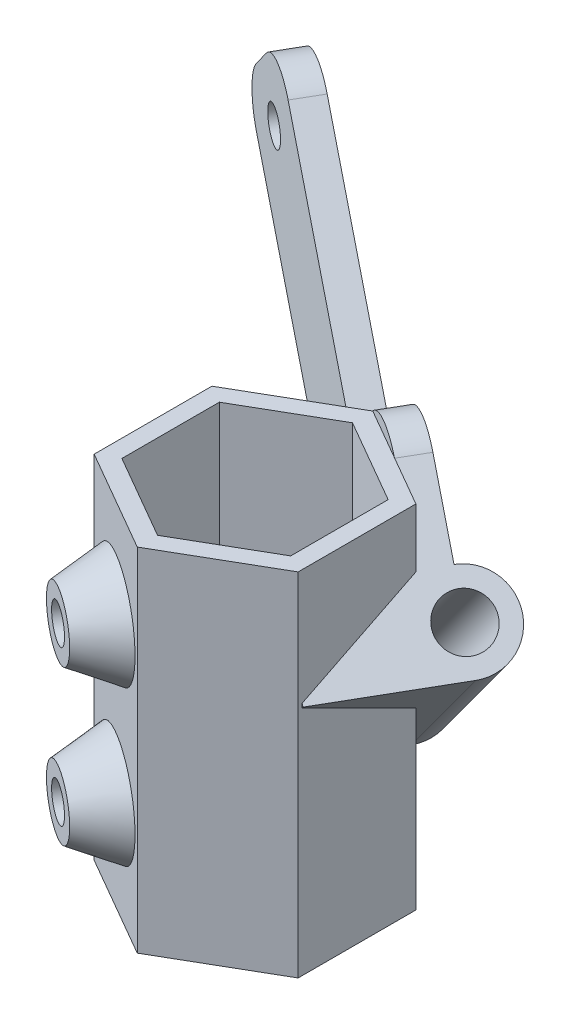
SolidWorks part; units mm, degrees
ref_plane "Plano frontal" through (0, 0, 0) normal (0, 0, 1) x (1, 0, 0)
ref_plane "Plano superior" through (0, 0, 0) normal (0, 1, 0) x (1, 0, 0)
ref_plane "Plano direito" through (0, 0, 0) normal (1, 0, 0) x (0, 0, -1)
sketch "Esboço1" plane through (0, 0, 0) normal (0, 1, 0) x (1, 0, 0)
  line L0 (0, 16.3256) -> (0, -14.1372) construction
  line L2 (7.25, 4.1858) -> (0, 8.3716)
  line L3 (0, 8.3716) -> (-7.25, 4.1858)
  line L4 (-7.25, 4.1858) -> (-7.25, -4.1858)
  line L5 (-7.25, -4.1858) -> (0, -8.3716)
  line L6 (0, -8.3716) -> (7.25, -4.1858)
  line L7 (7.25, -4.1858) -> (7.25, 4.1858)
  circle A0 centre (0, 0) radius 7.25 construction
  dimension "D1" = 14.5
extrude "Ressalto-extrusão1" add sketch "Esboço1" along normal blind 25
sketch "Esboço3" plane through (-3.625, 0, 6.2787) normal (-0.5, 0, 0.866) x (0.866, 0, 0.5)
  line L0 (0, -3.2486) -> (0, 27.6023) construction
  line L1 (-4.1858, 0) -> (4.1858, 0) construction
  line L2 (-11.1774, 12.5) -> (14.0862, 12.5) construction
  circle A0 centre (0, 7) radius 2.25
  circle A1 centre (0, 18) radius 2.25
  dimension "D1" = 4.5
  dimension "D2" = 7
extrude "Ressalto-extrusão2" add sketch "Esboço3" along normal blind 3
ref_plane "Plano1" through (0, 18, 0) normal (0, 1, 0) x (1, 0, 0)
sketch "Esboço4" plane through (0, 18, 0) normal (0, 1, 0) x (1, 0, 0)
  line L0 (-7.0736, -7.7518) -> (-6.8726, -4.4037)
  line L1 (-7.25, -4.1858) -> (0, -8.3716) construction
  line L2 (-6.8726, -4.4037) -> (-5.5736, -5.1537)
  line L3 (-5.5736, -5.1537) -> (-7.0736, -7.7518)
  line L4 (-2.5653, -4.4432) -> (-6.112, -10.5863) construction
  dimension "D1" = 1.5
revolve "Revolução1" add sketch "Esboço4" angle 360 about L4
ref_plane "Plano2" through (0, 7, 0) normal (0, -1, 0) x (-1, 0, 0)
sketch "Esboço5" plane through (0, 7, 0) normal (0, -1, 0) x (-1, 0, 0)
  line L0 (7.0736, -7.7518) -> (5.5736, -5.1537)
  line L1 (5.5736, -5.1537) -> (6.8726, -4.4037)
  line L2 (7.25, -4.1858) -> (0, -8.3716) construction
  line L3 (6.8726, -4.4037) -> (7.0736, -7.7518)
  line L4 (5.5736, -9.6537) -> (1.9867, -3.4411) construction
  dimension "D1" = 1.5
revolve "Revolução2" add sketch "Esboço5" angle 360 about L4
sketch "Esboço6" plane through (-5.125, 0, 8.8768) normal (-0.5, 0, 0.866) x (0.866, 0, 0.5)
  line L0 (0, 23.2309) -> (0, 1.0123) construction
  line L1 (4.2911, 18) -> (-4.8168, 18) construction
  line L2 (7.975, 18) -> (-7.975, 18) construction
  line L3 (4.1858, 12.5) -> (-4.1858, 12.5) construction
  line L4 (4.1858, 25) -> (4.1858, 0) construction
  line L5 (-4.1858, 25) -> (-4.1858, 0) construction
  circle A0 centre (0, 18) radius 1.25
  circle A1 centre (0, 7) radius 1.25
  dimension "D1" = 2.5
extrude "Corte-extrusão2" cut sketch "Esboço6" against normal blind 10
sketch "Esboço8" plane through (3.625, 0, -6.2787) normal (0.5, 0, -0.866) x (-0.866, 0, -0.5)
  line L0 (0, -2.0151) -> (0, 23.9668) construction
  line L1 (-8.3716, 25) -> (-8.3716, 0) construction
  line L6 (-8.3716, 12.5) -> (8.3716, 12.5) construction
  line L11 (8.3716, 25) -> (8.3716, 0) construction
  line L12 (-3.7, 16.2) -> (3.7, 8.8) construction
  line L13 (-3.4587, 9.0413) -> (3.4587, 15.9587) construction
  line L14 (-4.1289, 20.8716) -> (8.3716, 8.3711)
  line L15 (-8.3716, 16.6289) -> (4.1289, 4.1284)
  line L16 (-8.3716, 16.6289) -> (-4.1289, 20.8716)
  line L17 (4.1289, 4.1284) -> (8.3716, 8.3711)
  point P10 (0, 12.5)
  point P17 (0, 12.5)
  point P20 (2.1213, 14.6213)
  point P21 (0, 12.5)
  point P24 (2.1213, 14.6213)
  dimension "D2" = 45
  dimension "D3" = 3
extrude "Ressalto-extrusão3" add sketch "Esboço8" along normal blind 5 and the other way blind 7
sketch "Esboço2" plane through (0, 25, 0) normal (0, 1, 0) x (1, 0, 0)
  line L1 (0, 6.9282) -> (-6, 3.4641)
  line L2 (-6, 3.4641) -> (-6, -3.4641)
  line L3 (-6, -3.4641) -> (0, -6.9282)
  line L4 (0, -6.9282) -> (6, -3.4641)
  line L5 (6, -3.4641) -> (6, 3.4641)
  line L6 (6, 3.4641) -> (0, 6.9282)
  circle A0 centre (0, 0) radius 6 construction
extrude "Corte-extrusão1" cut sketch "Esboço2" against normal through all
fillet "Filete1" radius 3 2 edges at (7.9621, 10.3787, -9.5482) (4.2879, 14.6213, -11.6695)
sketch "Esboço9" plane through (-0.0002, -0.0003, -0.0001) normal (-0.6124, -0.7071, -0.3536) x (0.7906, -0.5477, -0.2739)
  line L0 (0.901, -15.079) -> (-6.3797, -6.1619) construction
  line L1 (-9.0122, -7.6812) -> (-3.3201, -14.6526) construction
  circle A0 centre (-0.9963, -12.7552) radius 1.75
  dimension "D1" = 3.5
  dimension "D2" = 3
extrude "Corte-extrusão3" cut sketch "Esboço9" against normal through all
sketch "Esboço10" plane through (-7.2498, 8.3713, -4.1857) normal (-0.6124, 0.7071, -0.3536) x (0.7906, 0.5477, -0.2739)
  line L0 (5.8499, 7.1653) -> (4.585, 5.6161)
  line L1 (4.585, 5.6161) -> (18.2786, -5.5647)
  line L2 (18.2786, -5.5647) -> (9.1703, 1.8722) construction
  line L3 (18.2786, -5.5647) -> (19.5436, -4.0156)
  line L5 (19.5436, -4.0156) -> (5.8499, 7.1653)
extrude "Ressalto-extrusão4" add sketch "Esboço10" along normal blind 8.8
sketch "Esboço13" plane through (-12.6387, 14.5939, -7.2969) normal (-0.6124, 0.7071, -0.3536) x (0.7906, 0.5477, -0.2739)
  line L0 (4.585, 5.6161) -> (5.8499, 7.1653)
  line L1 (5.8499, 7.1653) -> (12.6967, 1.5748)
  line L2 (19.5436, -4.0156) -> (5.8499, 7.1653) construction
  line L3 (12.6967, 1.5748) -> (11.4109, 0)
  line L4 (11.4109, 0) -> (4.585, 5.6161)
extrude "Ressalto-extrusão5" add sketch "Esboço13" along normal blind 20.2
sketch "Esboço14" plane through (3.6416, 0.0192, -6.269) normal (-0.5023, -0.0026, 0.8647) x (0.8647, -0.0015, 0.5023)
  line L0 (-19.8665, 26.0074) -> (-10.3837, 16.5538) construction
  line L1 (-28.9412, 28.8135) -> (-22.7005, 35.0734) construction
  circle A0 centre (-23.3421, 29.4724) radius 1.25
  dimension "D1" = 2.5
  dimension "D2" = 3.5
extrude "Corte-extrusão4" cut sketch "Esboço14" against normal through all
fillet "Filete2" radius 3 2 edges at (-20.8838, 28.8772, -21.5835) (-15.4792, 35.1274, -18.4441)
fillet "Filete3" radius 3 1 edges at (2.3119, 27.0941, -8.1915)
